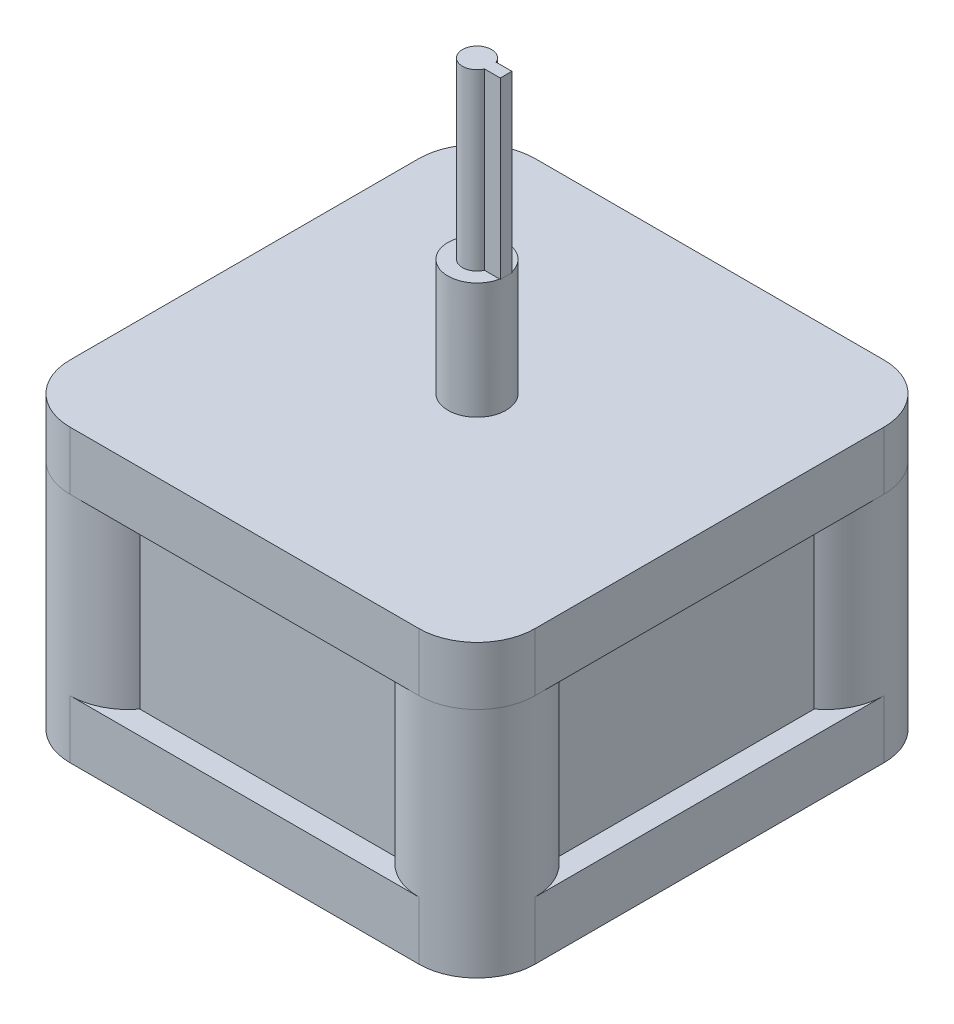
SolidWorks part; units mm, degrees
ref_plane "Front Plane" through (0, 0, 0) normal (0, 0, 1) x (1, 0, 0)
ref_plane "Top Plane" through (0, 0, 0) normal (0, 1, 0) x (1, 0, 0)
ref_plane "Right Plane" through (0, 0, 0) normal (1, 0, 0) x (0, 0, -1)
sketch "Sketch1" plane through (0, 0, 0) normal (0, 1, 0) x (1, 0, 0)
  line L1 (0, 0) -> (50.8, 0)
  line L2 (0, 0) -> (0, 50.8)
  line L3 (0, 50.8) -> (50.8, 50.8)
  line L4 (50.8, 0) -> (50.8, 50.8)
  dimension "D1" = 50.8
  dimension "D2" = 50.8
extrude "Boss-Extrude1" add sketch "Sketch1" along normal blind 6.35
fillet "Fillet1" radius 6.35 4 edges at (0, 3.175, -50.8) (50.8, 3.175, -50.8) (50.8, 3.175, 0) (0, 3.175, 0)
sketch "Sketch3" plane through (0, 6.35, 0) normal (0, 1, 0) x (1, 0, 0)
  line L0 (0, 44.45) -> (0, 6.35) construction
  line L1 (11.43, 48.26) -> (39.37, 48.26)
  line L2 (2.54, 39.37) -> (2.54, 11.43)
  line L3 (11.43, 2.54) -> (39.37, 2.54)
  line L4 (48.26, 39.37) -> (48.26, 11.43)
  line L5 (6.35, 0) -> (44.45, 0) construction
  arc A4 (11.43, 48.26) -> (2.54, 39.37) centre (6.35, 44.45) ccw
  arc A5 (48.26, 39.37) -> (39.37, 48.26) centre (44.45, 44.45) ccw
  arc A6 (2.54, 11.43) -> (11.43, 2.54) centre (6.35, 6.35) ccw
  arc A7 (39.37, 2.54) -> (48.26, 11.43) centre (44.45, 6.35) ccw
  dimension "D5" = 12.7
  dimension "D10" = 12.7
  dimension "D11" = 12.7
  dimension "D12" = 12.7
  dimension "D2" = 27.94
  dimension "D3" = 2.54
  dimension "D4" = 2.54
  dimension "D6" = 3.81
  dimension "D7" = 3.81
  dimension "D8" = 3.81
  dimension "D9" = 3.81
  dimension "D13" = 3.81
  dimension "D14" = 3.81
  dimension "D15" = 3.81
  dimension "D16" = 3.81
  dimension "D17" = 27.94
extrude "Boss-Extrude2" add sketch "Sketch3" along normal blind 19.05
sketch "Sketch5" plane through (0, 25.4, 0) normal (0, 1, 0) x (1, 0, 0)
  line L0 (2.54, 39.37) -> (2.54, 11.43) construction
  line L1 (0, 50.8) -> (50.8, 50.8)
  line L2 (0, 50.8) -> (0, 0)
  line L3 (0, 0) -> (50.8, 0)
  line L4 (50.8, 50.8) -> (50.8, 0)
  line L5 (11.43, 2.54) -> (39.37, 2.54) construction
  dimension "D1" = 50.8
  dimension "D2" = 50.8
  dimension "D3" = 2.54
  dimension "D4" = 2.54
extrude "Boss-Extrude3" add sketch "Sketch5" along normal blind 6.35
fillet "Fillet2" radius 6.35 4 edges at (50.8, 28.575, -50.8) (0, 28.575, -50.8) (50.8, 28.575, 0) (0, 28.575, 0)
sketch "Sketch6" plane through (0, 31.75, 0) normal (0, 1, 0) x (1, 0, 0)
  line L0 (6.35, 0) -> (44.45, 0) construction
  line L1 (0, 44.45) -> (0, 6.35) construction
  circle A0 centre (25.4, 25.4) radius 3.175
  dimension "D3" = 6.35
  dimension "D1" = 25.4
  dimension "D2" = 25.4
extrude "Boss-Extrude4" add sketch "Sketch6" along normal blind 12.7
sketch "Sketch7" plane through (0, 44.45, 0) normal (0, 1, 0) x (1, 0, 0)
  line L0 (28.575, 26.035) -> (28.575, 24.765)
  line L1 (28.575, 24.765) -> (26.855, 24.765)
  line L2 (28.575, 26.035) -> (26.855, 26.035)
  arc A0 (26.855, 26.035) -> (26.855, 24.765) centre (25.4, 25.4) ccw
  dimension "D1" = 3.175
  dimension "D2" = 1.27
  dimension "D3" = 0.635
  dimension "D4" = 3.175
extrude "Boss-Extrude5" add sketch "Sketch7" along normal blind 19.05
